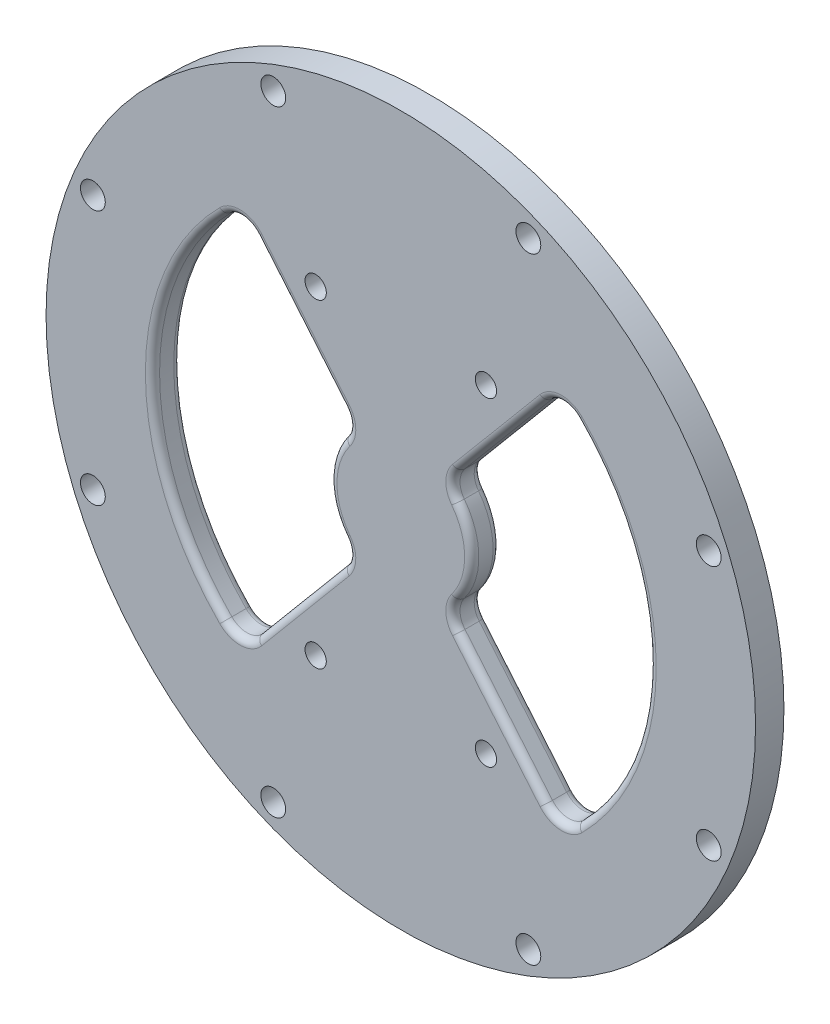
SolidWorks part; units mm, degrees
material "PLA"
ref_plane "Front" through (0, 0, 0) normal (0, 0, 1) x (1, 0, 0)
ref_plane "Top" through (0, 0, 0) normal (0, 1, 0) x (1, 0, 0)
ref_plane "Right" through (0, 0, 0) normal (1, 0, 0) x (0, 0, -1)
sketch "草图1" plane through (0, 0, 0) normal (0, 0, 1) x (1, 0, 0)
  circle A0 centre (0, 0) radius 50
  dimension "D1" = 100
extrude "凸台-拉伸1" add sketch "草图1" along normal blind 4
sketch "草图2" plane through (0, 0, 4) normal (0, 0, 1) x (1, 0, 0)
  line L0 (-1000, 0) -> (49000, 0) construction
  line L1 (0, -1000) -> (0, 49000) construction
  line L2 (382.6747, -923.8585) -> (-18751.4969, 45270.1181) construction
  circle A9 centre (0, 0) radius 47 construction
  circle A10 centre (-17.9764, 43.3989) radius 1.75
  circle A11 centre (17.9764, 43.3989) radius 1.75
  circle A12 centre (43.3989, 17.9764) radius 1.75
  circle A13 centre (43.3989, -17.9764) radius 1.75
  circle A14 centre (17.9764, -43.3989) radius 1.75
  circle A15 centre (-17.9764, -43.3989) radius 1.75
  circle A16 centre (-43.3989, -17.9764) radius 1.75
  circle A17 centre (-43.3989, 17.9764) radius 1.75
  point P3 (-17.9764, 43.3989)
  dimension "D1" = 94
  dimension "D3" = 3.5
  dimension "D2" = 22.5
  dimension "D4" = 8
sketch "草图3" plane through (0, 0, 4) normal (0, 0, 1) x (1, 0, 0)
  line L0 (-8.0461, 9.8021) -> (-20.3818, 24.5032)
  line L1 (-12, 22.5) -> (12, 22.5) construction
  line L2 (-12, 22.5) -> (-12, -22.5) construction
  line L3 (-12, -22.5) -> (12, -22.5) construction
  line L4 (12, 22.5) -> (12, -22.5) construction
  line L5 (-12, 22.5) -> (12, -22.5) construction
  line L6 (-12, -22.5) -> (12, 22.5) construction
  line L7 (0, 0) -> (40.498, 0) construction
  line L8 (0, 0) -> (0, -50000) construction
  line L9 (-8.0461, -9.8021) -> (-20.3818, -24.5032)
  line L10 (8.0461, -9.8021) -> (20.3818, -24.5032)
  line L11 (8.0461, 9.8021) -> (20.3818, 24.5032)
  circle A0 centre (-12, 22.5) radius 1.5
  circle A1 centre (-12, -22.5) radius 1.5
  circle A2 centre (12, -22.5) radius 1.5
  circle A3 centre (12, 22.5) radius 1.5
  arc A4 (-24.8061, 24.6912) -> (-24.8061, -24.6912) centre (0, 0) ccw
  arc A5 (-20.3818, -24.5032) -> (-24.8061, -24.6912) centre (-22.6799, -22.5748) cw
  arc A6 (-7.9571, 6.0567) -> (-7.9571, -6.0567) centre (0, 0) ccw
  arc A8 (20.3818, 24.5032) -> (24.8061, 24.6912) centre (22.6799, 22.5748) cw
  arc A9 (-8.0461, -9.8021) -> (-7.9571, -6.0567) centre (-10.3443, -7.8738) ccw
  arc A10 (-7.9571, 6.0567) -> (-8.0461, 9.8021) centre (-10.3443, 7.8738) ccw
  arc A11 (-20.3818, 24.5032) -> (-24.8061, 24.6912) centre (-22.6799, 22.5748) ccw
  arc A12 (24.8061, 24.6912) -> (24.8061, -24.6912) centre (0, 0) cw
  arc A13 (20.3818, -24.5032) -> (24.8061, -24.6912) centre (22.6799, -22.5748) ccw
  arc A14 (8.0461, -9.8021) -> (7.9571, -6.0567) centre (10.3443, -7.8738) cw
  arc A15 (7.9571, 6.0567) -> (7.9571, -6.0567) centre (0, 0) cw
  arc A16 (7.9571, 6.0567) -> (8.0461, 9.8021) centre (10.3443, 7.8738) cw
  point P0 (0, 0)
  point P25 (-22.3924, -26.8994)
  point P32 (-22.3924, 26.8994)
  dimension "D3" = 3
  dimension "D4" = 3
  dimension "D5" = 3
  dimension "D6" = 3
  dimension "D7" = 3
  dimension "D8" = 22.5
  dimension "D9" = 3
  dimension "D12" = 35
  dimension "D13" = 10
  dimension "D1" = 24
  dimension "D2" = 45
  dimension "D11" = 50
extrude "切除-拉伸1" cut sketch "草图3" against normal blind 4
fillet "圆角2" radius 1 32 edges at (22.5525, -25.5721, 0) (14.2139, -17.1527, 0) (7.3451, -7.945, 0) (10, 0, 0) (7.3451, 7.945, 0) (14.2139, 17.1527, 0) (22.5525, 25.5721, 0) (22.5525, -25.5721, 4) (14.2139, -17.1527, 4) (7.3451, -7.945, 4) (10, 0, 4) (7.3451, 7.945, 4) (14.2139, 17.1527, 4) (22.5525, 25.5721, 4) (-7.3451, 7.945, 0) (-10, 0, 0) (-7.3451, -7.945, 0) (-14.2139, -17.1527, 0) (-22.5525, -25.5721, 0) (-35, 0, 0) (-22.5525, 25.5721, 0) (-7.3451, 7.945, 4) (-10, 0, 4) (-7.3451, -7.945, 4) (-14.2139, -17.1527, 4) (-22.5525, -25.5721, 4) (-35, 0, 4) (-22.5525, 25.5721, 4) (35, 0, 0) (35, 0, 4) (-14.2139, 17.1527, 0) (-14.2139, 17.1527, 4)
extrude "切除-拉伸2" cut sketch "草图2" against normal blind 10
